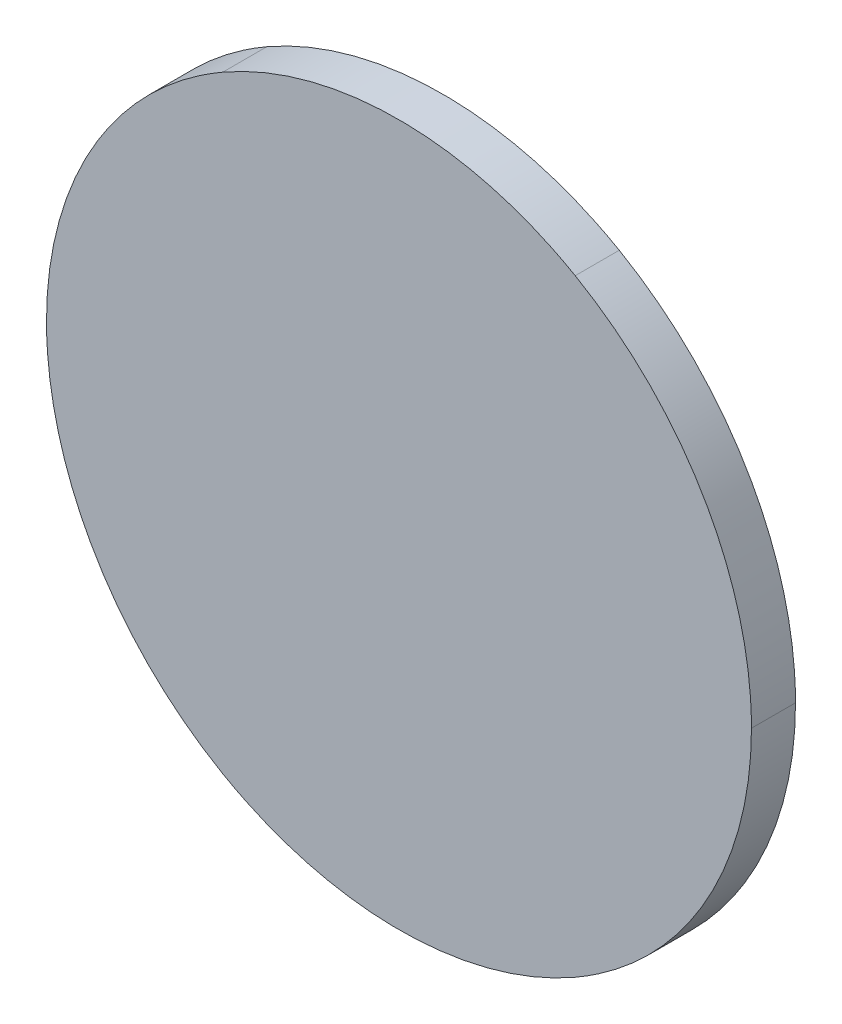
SolidWorks part; units mm, degrees
ref_plane "Front Plane" through (0, 0, 0) normal (0, 0, 1) x (1, 0, 0)
ref_plane "Top Plane" through (0, 0, 0) normal (0, 1, 0) x (1, 0, 0)
ref_plane "Right Plane" through (0, 0, 0) normal (1, 0, 0) x (0, 0, -1)
sketch "Sketch1" plane through (0, 0, 0) normal (0, 0, 1) x (1, 0, 0)
  line L0 (22.2431, 7900.1141) -> (22.2664, 7895.9158)
  line L1 (22.2664, 7895.9158) -> (22.2431, 7900.1141)
  line L2 (28.5176, 7900.0918) -> (28.4943, 7895.8935)
  line L3 (28.4943, 7895.8935) -> (28.5176, 7900.0918)
  line L4 (41.0237, 7919.9935) -> (9.7944, 7919.7265) construction
  line L5 (25.4143, 7910.0622) -> (25.3783, 7932.6582) construction
  line L6 (50.8286, 7910.0622) -> (0, 7910.0622) construction
  circle A0 centre (25.4091, 7919.86) radius 15.6152
  circle A1 centre (25.4143, 7910.0622) radius 22.5961
  spline S0 degree 3 poles (50.8286, 7910.0622) (50.8286, 7901.0262) (45.9847, 7892.6766) (38.1215, 7888.1585) knots 0 0 0 0 1 1 1 1
  spline S1 degree 3 poles (38.1215, 7888.1585) (30.2582, 7883.6405) (20.5704, 7883.6405) (12.7072, 7888.1585) knots 0 0 0 0 1 1 1 1
  spline S2 degree 3 poles (12.7072, 7888.1585) (4.8439, 7892.6766) (0, 7901.0262) (0, 7910.0622) knots 0 0 0 0 1 1 1 1
  spline S3 degree 3 poles (0, 7910.0622) (0, 7919.0982) (4.8439, 7927.4478) (12.7072, 7931.9658) knots 0 0 0 0 1 1 1 1
  spline S4 degree 3 poles (12.7072, 7931.9658) (20.5704, 7936.4838) (30.2582, 7936.4838) (38.1215, 7931.9658) knots 0 0 0 0 1 1 1 1
  spline S5 degree 3 poles (38.1215, 7931.9658) (45.9847, 7927.4478) (50.8286, 7919.0982) (50.8286, 7910.0622) knots 0 0 0 0 1 1 1 1
  spline S11 degree 3 poles (25.4527, 7904.2601) (16.8463, 7904.2363) (9.8432, 7911.1536) (9.7944, 7919.7265) knots 0 0 0 0 1 1 1 1
  spline S12 degree 3 poles (9.7944, 7919.7265) (9.7456, 7928.2994) (16.6694, 7935.2954) (25.2755, 7935.369) knots 0 0 0 0 1 1 1 1
  spline S13 degree 3 poles (25.2755, 7935.369) (33.8815, 7935.4425) (40.9249, 7928.5659) (41.0237, 7919.9935) knots 0 0 0 0 1 1 1 1
  spline S14 degree 3 poles (22.2664, 7895.9158) (18.2625, 7895.7998) (14.5448, 7896.2979) (10.9506, 7897.3638) knots 0 0 0 0 1 1 1 1
  spline S15 degree 3 poles (10.9506, 7897.3638) (8.4873, 7901.2979) (7.4082, 7905.7059) (8.1988, 7910.8247) knots 0 0 0 0 1 1 1 1
  spline S16 degree 3 poles (8.1988, 7910.8247) (9.6577, 7907.2264) (14.1595, 7902.1528) (22.2431, 7900.1141) knots 0 0 0 0 1 1 1 1
  spline S17 degree 3 poles (28.4943, 7895.8935) (32.4875, 7895.7774) (36.1952, 7896.2755) (39.7797, 7897.3414) knots 0 0 0 0 1 1 1 1
  spline S18 degree 3 poles (39.7797, 7897.3414) (42.2364, 7901.2755) (43.3954, 7905.7662) (42.6069, 7910.8851) knots 0 0 0 0 1 1 1 1
  spline S19 degree 3 poles (42.6069, 7910.8851) (41.1519, 7907.2868) (36.5795, 7902.1304) (28.5176, 7900.0918) knots 0 0 0 0 1 1 1 1
  point P2 (25.4143, 7910.0622)
extrude "Boss-Extrude1" add sketch "Sketch1" along normal blind 3.175 contours S3 S4 S5 S0 S1 S2
sketch "Sketch3" plane through (0, 0, 0) normal (0, 0, 1) x (1, 0, 0)
  circle A0 centre (25.4143, 7910.0622) radius 22.5961
extrude "Boss-Extrude2" add sketch "Sketch3" against normal blind 0.0254
dome "Dome1" faces to dome 1 distance 6.35 reverse direction no elliptical dome no face at (48.0104, 7910.0622, -0.0254) parameters "D1"=6.35
sketch "Sketch4" plane through (0, 0, 0) normal (0, 0, 1) x (1, 0, 0)
  line L0 (28.5176, 7900.0918) -> (28.4943, 7895.8935) construction
  line L1 (22.2431, 7900.1141) -> (22.2664, 7895.9158) construction
  line L2 (28.5176, 7900.0918) -> (28.4943, 7895.8935)
  line L3 (22.2431, 7900.1141) -> (22.2664, 7895.9158)
  circle A0 centre (25.4091, 7919.86) radius 15.6152 construction
  circle A1 centre (25.4091, 7919.86) radius 15.6152
  spline S0 degree 3 poles (3037.4297, 7780.6721) (-3301.6498, 8083.0328) (3273.2482, 7441.3993) (-2851.8462, 8678.2712) knots -19.15749 -19.15749 -19.15749 -19.15749 14.877887 14.877887 14.877887 14.877887 only from (39.7797, 7897.3414) to (42.6069, 7910.8851) construction
  spline S1 degree 3 poles (-357.1375, 4942.7781) (67.7967, 10958.5231) (490.5035, 4912.7076) (-990.6089, 10706.9345) knots -8.359615 -8.359615 -8.359615 -8.359615 8.866414 8.866414 8.866414 8.866414 only from (42.6069, 7910.8851) to (28.5176, 7900.0918) construction
  spline S2 degree 3 poles (-2571.6151, 9389.3454) (2426.5864, 6810.0679) (-2421.3912, 8364.7526) (2980.6367, 8318.1021) knots -22.667208 -22.667208 -22.667208 -22.667208 27.188979 27.188979 27.188979 27.188979 only from (28.4943, 7895.8935) to (39.7797, 7897.3414) construction
  spline S3 degree 3 poles (2623.8359, 9386.8711) (-2376.309, 6812.0603) (2472.1139, 8363.7413) (-2930.0697, 8317.6525) knots -22.648714 -22.648714 -22.648714 -22.648714 27.165026 27.165026 27.165026 27.165026 only from (22.2664, 7895.9158) to (10.9506, 7897.3638) construction
  spline S4 degree 3 poles (298.9645, 4930.2788) (100.9196, 10951.9715) (-560.2746, 4939.1751) (1155.8374, 10662.7458) knots -8.483196 -8.483196 -8.483196 -8.483196 8.919154 8.919154 8.919154 8.919154 only from (8.1988, 7910.8247) to (22.2431, 7900.1141) construction
  spline S5 degree 3 poles (-2392.8153, 6141.6121) (3016.314, 9273.4811) (-2972.8971, 6573.4388) (2670.521, 9289.5986) knots -20.767769 -20.767769 -20.767769 -20.767769 15.433179 15.433179 15.433179 15.433179 only from (10.9506, 7897.3638) to (8.1988, 7910.8247) construction
  spline S6 degree 3 poles (39.7797, 7897.3414) (42.2364, 7901.2755) (43.3954, 7905.7662) (42.6069, 7910.8851) knots 0 0 0 0 1 1 1 1
  spline S7 degree 3 poles (42.6069, 7910.8851) (41.1519, 7907.2868) (36.5795, 7902.1304) (28.5176, 7900.0918) knots 0 0 0 0 1 1 1 1
  spline S8 degree 3 poles (28.4943, 7895.8935) (32.4875, 7895.7774) (36.1952, 7896.2755) (39.7797, 7897.3414) knots 0 0 0 0 1 1 1 1
  spline S9 degree 3 poles (22.2664, 7895.9158) (18.2625, 7895.7998) (14.5448, 7896.2979) (10.9506, 7897.3638) knots 0 0 0 0 1 1 1 1
  spline S10 degree 3 poles (8.1988, 7910.8247) (9.6577, 7907.2264) (14.1595, 7902.1528) (22.2431, 7900.1141) knots 0 0 0 0 1 1 1 1
  spline S11 degree 3 poles (10.9506, 7897.3638) (8.4873, 7901.2979) (7.4082, 7905.7059) (8.1988, 7910.8247) knots 0 0 0 0 1 1 1 1
extrude "Cut-Extrude1" cut sketch "Sketch4" against normal blind 7.6454
